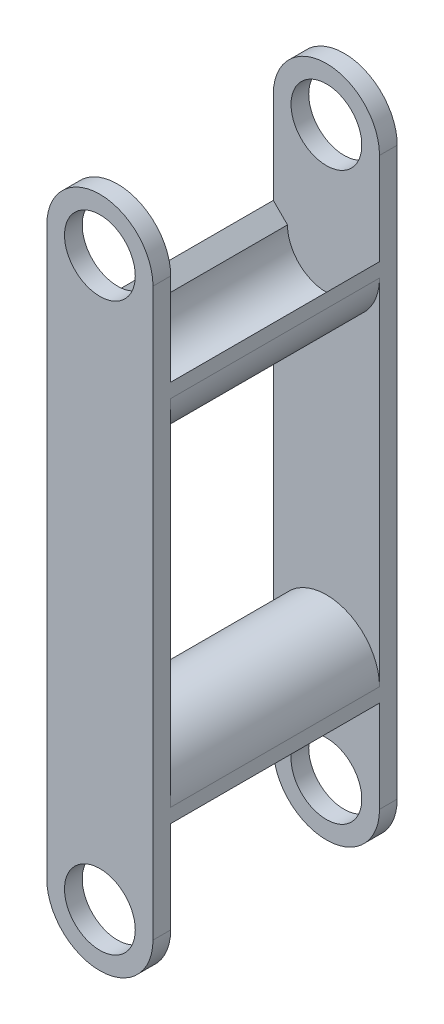
SolidWorks part; units mm, degrees
ref_plane "Front Plane" through (0, 0, 0) normal (0, 0, 1) x (1, 0, 0)
ref_plane "Top Plane" through (0, 0, 0) normal (0, 1, 0) x (1, 0, 0)
ref_plane "Right Plane" through (0, 0, 0) normal (1, 0, 0) x (0, 0, -1)
sketch "Sketch2" plane through (0, 0, 0) normal (0, 0, 1) x (1, 0, 0)
  line L2 (-15, 0) -> (-15, 30)
  line L4 (15, 0) -> (15, 30)
  circle A0 centre (0, 0) radius 10
  arc A1 (-15, 0) -> (15, 0) centre (0, 0) ccw
  arc A2 (15, 30) -> (-15, 30) centre (0, 30) ccw
  dimension "D1" = 30
  dimension "D2" = 5
  dimension "D3" = 30
extrude "Boss-Extrude2" add sketch "Sketch2" along normal blind 5
sketch "Sketch3" plane through (0, 0, 0) normal (0, 0, -1) x (-1, 0, 0)
  line L2 (-15, 30) -> (-15, 26)
  line L3 (-15, 0) -> (-15, 30) construction
  line L4 (-15, 26) -> (-11, 30)
  line L5 (15, 30) -> (15, 26)
  line L6 (15, 30) -> (15, 0) construction
  line L7 (15, 26) -> (11, 30)
  arc A0 (15, 30) -> (-15, 30) centre (0, 30) ccw
  arc A1 (11, 30) -> (-11, 30) centre (0, 30) ccw
  dimension "D1" = 4
  dimension "D2" = 4
  dimension "D3" = 4
extrude "Boss-Extrude3" add sketch "Sketch3" along normal blind 59
sketch "Sketch4" plane through (0, 0, -59) normal (0, 0, -1) x (-1, 0, 0)
  line L0 (-15, 30) -> (-15, 0)
  line L1 (15, 30) -> (15, 0)
  arc A0 (15, 30) -> (-15, 30) centre (0, 30) ccw
  arc A1 (-15, 0) -> (15, 0) centre (0, 0) ccw
  circle A2 centre (0, 0) radius 10
extrude "Boss-Extrude4" add sketch "Sketch4" along normal blind 5
sketch "Sketch5" plane through (0, 0, 5) normal (0, 0, 1) x (1, 0, 0)
  line L0 (-15, 80) -> (15, 80) construction
  line L1 (-15, 0) -> (-10, 0)
  line L2 (-15, 0) -> (-15, 160)
  line L3 (-15, 160) -> (15, 160)
  line L4 (15, 0) -> (15, 160)
  line L5 (10, 0) -> (15, 0)
  circle A0 centre (0, 0) radius 10
  line M6 (15, 0) -> (15, 30)
  arc M7 (15, 30) -> (-15, 30) centre (0, 30) ccw
  line M8 (-15, 30) -> (-15, 0)
  circle M9 centre (0, 0) radius 10
  dimension "D1" = 160
extrude "Boss-Extrude5" add sketch "Sketch5" against normal blind 5 contours L0 L2 L4 M7 | L2 L0 L4 L3 | L5 L1 M9 M6 M7 M8 region at (0, 120, 5) region at (0, 60.7438, 5) region at (0, 23.4288, 5)
ref_plane "Plane1" through (0, 80, 0) normal (0, 1, 0) x (1, 0, 0)
mirror "Mirror1" about plane through (0, 80, 0) normal (0, 1, 0) of "Boss-Extrude3", "Boss-Extrude4", "Boss-Extrude2"
sketch "Sketch6" plane through (0, 0, 5) normal (0, 0, 1) x (1, 0, 0)
  line L0 (-10, 160) -> (10, 160) construction
  circle A0 centre (0, 160) radius 10
extrude "Cut-Extrude1" cut sketch "Sketch6" against normal blind 5
ref_plane "Plane2" through (0, 0, -29.5) normal (0, 0, -1) x (-1, 0, 0)
mirror "Mirror2" about plane through (0, 0, -29.5) normal (0, 0, -1) of "Cut-Extrude1", "Boss-Extrude5"
